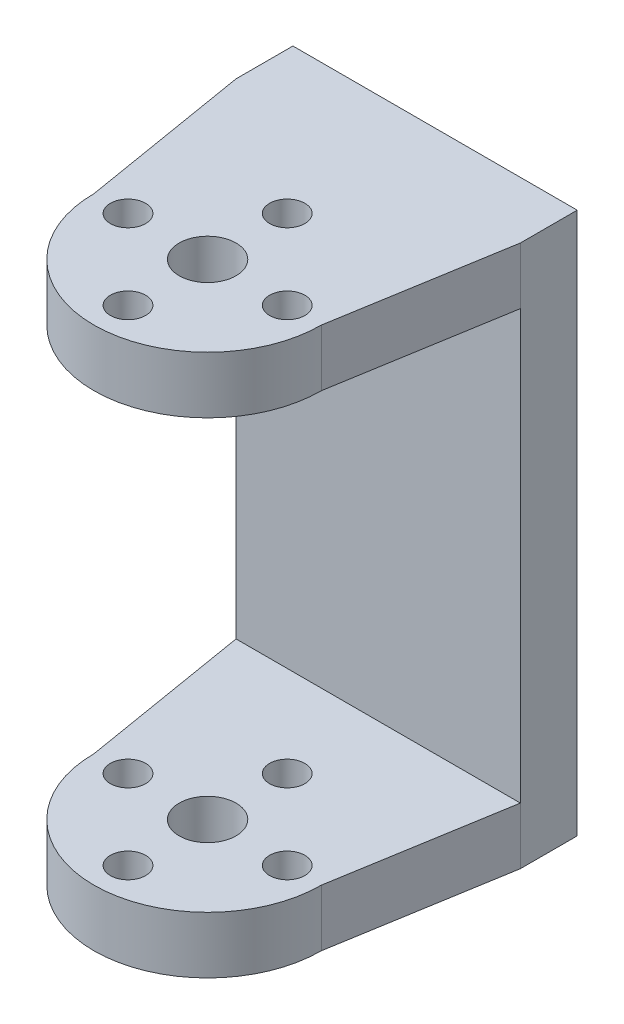
SolidWorks part; units mm, degrees
ref_plane "Front Plane" through (0, 0, 0) normal (0, 0, 1) x (1, 0, 0)
ref_plane "Top Plane" through (0, 0, 0) normal (0, 1, 0) x (1, 0, 0)
ref_plane "Right Plane" through (0, 0, 0) normal (1, 0, 0) x (0, 0, -1)
sketch "Sketch1" plane through (0, 0, 0) normal (0, 1, 0) x (1, 0, 0)
  line L0 (-12.5, 15) -> (-10, 0)
  line L2 (-12.5, 15) -> (-12.5, 20)
  line L3 (-12.5, 20) -> (12.5, 20)
  line L4 (12.5, 15) -> (12.5, 20)
  line L5 (12.5, 15) -> (10, 0)
  circle A3 centre (0, 0) radius 2.5
  arc A4 (-10, 0) -> (10, 0) centre (0, 0) ccw
  point P12 (-12.5, 0)
  point P13 (0, 20)
  dimension "D3" = 0
  dimension "D4" = 20
  dimension "D6" = 5
  dimension "D1" = 25
  dimension "D2" = 20
  dimension "D5" = 5
extrude "Boss-Extrude1" add sketch "Sketch1" along normal blind 47.65
sketch "Sketch2" plane through (-12.5, 0, 0) normal (-1, 0, 0) x (0, 0, 1)
  line L1 (25, 5) -> (-15, 5)
  line L2 (25, 5) -> (25, 42.65)
  line L3 (25, 42.65) -> (-15, 42.65)
  line L4 (-15, 5) -> (-15, 42.65)
  line L5 (-20, 47.65) -> (-20, 0) construction
  point P6 (-20, 23.825)
  point P7 (25, 23.825)
  dimension "D1" = 37.65
  dimension "D2" = 5
  dimension "D3" = 45
extrude "Cut-Extrude1" cut sketch "Sketch2" against normal through all
ref_plane "B mid plane" through (0, 23.825, 0) normal (0, -1, 0) x (-1, 0, 0)
sketch "Sketch3" plane through (0, 47.65, 0) normal (0, 1, 0) x (1, 0, 0)
  circle A0 centre (0, 7) radius 1.55
  circle A1 centre (0, 0) radius 2.5 construction
  dimension "D1" = 3.1
  dimension "D2" = 7
  dimension "D3" = 0
extrude "Cut-Extrude2" cut sketch "Sketch3" against normal through all
ref_axis "Axis1" through (0, 47.65, 0) along (0, -1, 0)
pattern_circular "CirPattern1" count 4 over 360 about axis through (0, 47.65, 0) along (0, -1, 0) of "Cut-Extrude2"
